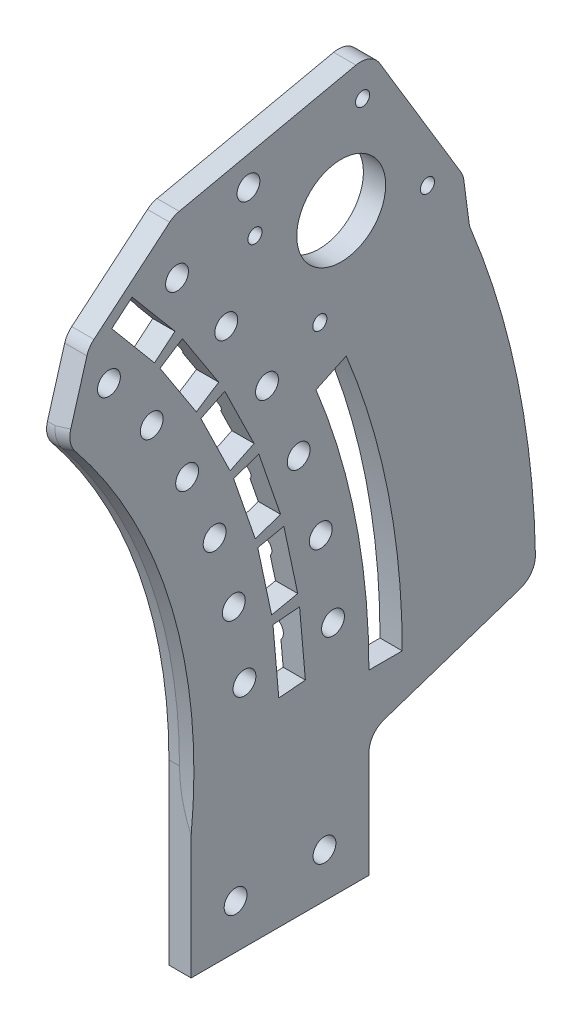
SolidWorks part; units mm, degrees
other "Markup1"
sketch "Sketch5" plane through (7.4724, -50.8, -116.7452) normal (0.7166, -0.0822, 0.6926) x (0.6913, -0.0479, -0.721)
other "Markup2"
sketch "Sketch6" plane through (7.4724, -50.8, -116.7452) normal (0.7166, -0.0822, 0.6926) x (0.6913, -0.0479, -0.721)
material "6061-T6 (SS)"
ref_plane "Front Plane" through (0, 0, 0) normal (0, 0, 1) x (1, 0, 0)
ref_plane "Top Plane" through (0, 0, 0) normal (0, 1, 0) x (1, 0, 0)
ref_plane "Right Plane" through (0, 0, 0) normal (1, 0, 0) x (0, 0, -1)
sketch "Sketch1" plane through (0, 0, 0) normal (1, 0, 0) x (0, 0, -1)
  line L0 (0, 0) -> (152.4, 0) construction
  line L1 (0, 0) -> (116.7452, 97.9608) construction
  line L2 (152.4, 0) -> (152.4, -50.8)
  line L3 (152.4, -50.8) -> (203.2, -50.8)
  line L4 (203.2, -50.8) -> (203.2, 0) construction
  line L5 (116.7452, 97.9608) -> (148.2956, 124.4347) construction
  line L6 (152.4, 0) -> (203.2, 0) construction
  line L7 (116.7452, 97.9608) -> (148.2956, 124.4347) construction
  line L8 (0, 0) -> (177.1234, 15.4963) construction
  line L9 (0, 0) -> (0, 168.3639) construction
  line L10 (177.1234, 15.4963) -> (183.4493, 16.0497) construction
  line L11 (0, 0) -> (175.0988, 30.8746) construction
  line L12 (0, 0) -> (171.7416, 46.018) construction
  line L13 (0, 0) -> (167.0773, 60.8112) construction
  line L14 (0, 0) -> (161.1415, 75.1415) construction
  line L15 (0, 0) -> (153.9793, 88.9) construction
  line L16 (0, 0) -> (145.6452, 101.9819) construction
  line L17 (0, 0) -> (175.0988, 30.8746) construction
  line L18 (0, 0) -> (171.7416, 46.018) construction
  line L19 (183.4493, 16.0497) -> (196.1009, 17.1566) construction
  line L20 (181.3523, 31.9773) -> (193.8594, 34.1826) construction
  line L21 (177.8752, 47.6615) -> (190.1425, 50.9485) construction
  line L22 (173.0444, 62.983) -> (184.9785, 67.3267) construction
  line L23 (166.8966, 77.8252) -> (178.4067, 83.1924) construction
  line L24 (159.4786, 92.075) -> (170.4771, 98.425) construction
  line L25 (150.8468, 105.6241) -> (161.2501, 112.9085) construction
  line L26 (0, 0) -> (183.4493, 16.0497) construction
  line L27 (0, 0) -> (181.3523, 31.9773) construction
  line L28 (152.4, -50.8) -> (152.4, -38.1) construction
  line L29 (152.4, -38.1) -> (203.2, -38.1) construction
  line L30 (0, 0) -> (42824.6192, 25807.9831) construction
  line L31 (195.2803, 117.6844) -> (182.1698, 139.4393) construction
  line L32 (195.2803, 117.6844) -> (208.3907, 95.9295) construction
  line L33 (217.0352, 130.7949) -> (203.9247, 152.5498)
  line L34 (217.0352, 130.7949) -> (230.1456, 109.04)
  line L36 (177.6941, 146.8661) -> (203.9247, 152.5498)
  line L37 (196.7125, 80.97) -> (212.8664, 88.5027) construction
  line L38 (188.0704, 76.9401) -> (212.8664, 88.5027) construction
  line L39 (212.8664, 88.5027) -> (230.1456, 109.04) construction
  line L40 (196.7125, 80.97) -> (188.0704, 76.9401)
  line L41 (203.2, 0) -> (212.725, 0)
  line L42 (203.2, -15.875) -> (250.825, 0)
  line L43 (230.1456, 109.04) -> (231.9445, 95.472)
  line L44 (203.2, -50.8) -> (203.2, -15.875)
  line L45 (195.2803, 117.6844) -> (190.7375, 99.3622) construction
  line L47 (0, 0) -> (136.2027, 114.2876) construction
  line L48 (116.7452, 97.9608) -> (123.1425, 119.9075)
  line L49 (123.1425, 119.9075) -> (147.4644, 140.316)
  line L50 (147.4644, 140.316) -> (177.6941, 146.8661)
  line L51 (189.1677, 93.0309) -> (195.2803, 117.6844) construction
  line L52 (195.2803, 117.6844) -> (201.3928, 142.3379) construction
  arc A0 (152.4, 0) -> (116.7452, 97.9608) centre (0, 0) ccw
  arc A1 (203.2, 0) -> (188.0704, 76.9401) centre (0, 0) ccw
  circle A2 centre (177.1234, 15.4963) radius 6.35 construction
  arc A4 (183.4493, 16.0497) -> (141.0671, 118.3693) centre (0, 0) ccw construction
  arc A5 (189.7751, 16.6032) -> (145.9315, 122.451) centre (0, 0) ccw construction
  circle A7 centre (196.1009, 17.1566) radius 6.35 construction
  circle A9 centre (175.0988, 30.8746) radius 6.35 construction
  circle A11 centre (171.7416, 46.018) radius 6.35 construction
  circle A13 centre (167.0773, 60.8112) radius 6.35 construction
  circle A15 centre (161.1415, 75.1415) radius 6.35 construction
  circle A17 centre (153.9793, 88.9) radius 6.35 construction
  circle A19 centre (145.6452, 101.9819) radius 6.35 construction
  circle A21 centre (193.8594, 34.1826) radius 6.35 construction
  circle A23 centre (190.1425, 50.9485) radius 6.35 construction
  circle A25 centre (184.9785, 67.3267) radius 6.35 construction
  circle A27 centre (178.4067, 83.1924) radius 6.35 construction
  circle A29 centre (170.4771, 98.425) radius 6.35 construction
  circle A31 centre (161.2501, 112.9085) radius 6.35 construction
  circle A32 centre (165.1, -38.1) radius 3.2639
  circle A33 centre (190.5, -38.1) radius 3.2639
  circle A34 centre (195.2803, 117.6844) radius 12.7
  circle A36 centre (208.3907, 95.9295) radius 2.0193 construction
  arc A37 (196.7125, 80.97) -> (212.725, 0) centre (0, 0) cw
  arc A38 (231.9445, 95.472) -> (250.825, 0) centre (0, 0) cw
  circle A41 centre (170.6267, 123.797) radius 2.0193
  circle A42 centre (201.3928, 142.3379) radius 2.0193
  circle A45 centre (195.2803, 117.6844) radius 12.7
  circle A46 centre (219.9338, 111.5719) radius 2.0193
  circle A47 centre (195.2803, 117.6844) radius 12.7
  circle A48 centre (189.1677, 93.0309) radius 2.0193
  circle A49 centre (195.2803, 117.6844) radius 12.7
  point P11 (151.8201, 13.2825)
  point P24 (150.0847, 26.464)
  point P82 (217.0352, 130.7949)
  point P124 (195.2803, 117.6844)
  dimension "D5" = 12.7
  dimension "D7" = 22.86
  dimension "D12" = 12.7
  dimension "D24" = 6.5278
  dimension "D25" = 6.5278
  dimension "D28" = 25.4
  dimension "D30" = 25.4
  dimension "D32" = 4.0386
  dimension "D35" = 9.525
  dimension "D43" = 4.0386
  dimension "D1" = 152.4
  dimension "D2" = 40
  dimension "D3" = 50.8
  dimension "D4" = 50.8
  dimension "D6" = 5
  dimension "D8" = 25.4
  dimension "D10" = 90
  dimension "D13" = 25.4
  dimension "D14" = 5
  dimension "D16" = 5
  dimension "D17" = 6.35
  dimension "D20" = 5
  dimension "D21" = 12.7
  dimension "D22" = 12.7
  dimension "D23" = 12.7
  dimension "D26" = 8.925
  dimension "D27" = 228
  dimension "D29" = 25.4
  dimension "D31" = 25.4
  dimension "D33" = 25.4
  dimension "D34" = 25.4
  dimension "D37" = 15.875
  dimension "D38" = 45
  dimension "D41" = 12.7
  dimension "D42" = 31.75
  dimension "D9" = 6.35
  dimension "D36" = 38.1
  dimension "D15" = 6
  dimension "D19" = 7
  dimension "D45" = 4
extrude "Boss-Extrude1" add sketch "Sketch1" along normal blind 6.35 contours A38 L43 L34 L33 L36 L50 L49 L48 A0 L2 L3 L44 L42 A48 A46 A42 A41 A34 A33 A32 region at (0, 54.4796, -185.6582)
sketch "Sketch2" plane through (0, 0, 0) normal (0, 1, 0) x (1, 0, 0)
  line L0 (0, 0) -> (31.75, 0) construction
  line L1 (31.75, 0) -> (31.75, 38.1) construction
  line L2 (31.75, 38.1) -> (-86.106, 38.1)
  line L3 (-86.106, 38.1) -> (149.606, 38.1)
  arc A0 (149.606, 38.1) -> (-86.106, 38.1) centre (31.75, 38.1) ccw
  dimension "D3" = 235.712
  dimension "D1" = 31.75
  dimension "D2" = 38.1
revolve "Cut-Revolve1" cut sketch "Sketch2" angle 360 about L0 region at (31.75, 0, -88.1196)
fillet "Fillet1" radius 6.35 9 edges at (3.175, -15.875, -203.2) (3.175, 0, -250.825) (3.175, 95.472, -231.9445) (3.175, 109.04, -230.1456) (3.175, 152.5498, -203.9247) (3.175, 140.316, -147.4644) (3.175, 119.9075, -123.1425) (1.5088, 97.9608, -116.7452)
sketch "Sketch7" plane through (0, 0, 0) normal (0, 0, 1) x (1, 0, 0)
  line L0 (0, 0) -> (50000, 0) construction
sketch "Sketch8" plane through (0, 0, 0) normal (-1, 0, 0) x (0, 0, 1)
  line L0 (0, 0) -> (-192.938, 16.8799) construction
  line L1 (0, 0) -> (-81.6847, 0) construction
  line L2 (0, 0) -> (-189.4427, 40.2673) construction
  line L3 (0, 0) -> (-183.1233, 63.0544) construction
  line L4 (0, 0) -> (-174.0739, 84.9015) construction
  line L5 (0, 0) -> (-162.4295, 105.483) construction
  line L6 (0, 0) -> (-148.3637, 124.4919) construction
  line L7 (0, 0) -> (-167.6347, 14.6661) construction
  line L8 (0, 0) -> (-164.5978, 34.9863) construction
  line L9 (-177.4475, 5.9633) -> (-175.7872, 24.9408)
  line L10 (-175.7872, 24.9408) -> (-183.3782, 25.6049)
  line L11 (-183.3782, 25.6049) -> (-185.0385, 6.6274)
  line L12 (-185.0385, 6.6274) -> (-177.4475, 5.9633)
  line L13 (-182.8516, 29.1285) -> (-175.3981, 27.5442)
  line L14 (-175.3981, 27.5442) -> (-171.4374, 46.1779)
  line L15 (-171.4374, 46.1779) -> (-178.8909, 47.7622)
  line L16 (-178.8909, 47.7622) -> (-182.8516, 29.1285)
  line L17 (-177.9388, 51.1954) -> (-170.7339, 48.7146)
  line L18 (-170.7339, 48.7146) -> (-164.5318, 66.7267)
  line L19 (-164.5318, 66.7267) -> (-171.7367, 69.2075)
  line L20 (-171.7367, 69.2075) -> (-177.9388, 51.1954)
  line L21 (-170.3733, 72.4991) -> (-163.5245, 69.1587)
  line L22 (-163.5245, 69.1587) -> (-155.1735, 86.2807)
  line L23 (-155.1735, 86.2807) -> (-162.0223, 89.6211)
  line L24 (-162.0223, 89.6211) -> (-170.3733, 72.4991)
  line L25 (-160.2679, 92.722) -> (-153.8773, 88.5718)
  line L26 (-153.8773, 88.5718) -> (-143.5019, 104.5485)
  line L27 (-143.5019, 104.5485) -> (-149.8926, 108.6986)
  line L28 (-149.8926, 108.6986) -> (-160.2679, 92.722)
  line L29 (-147.7734, 111.5626) -> (-141.9361, 106.6645)
  line L30 (-141.9361, 106.6645) -> (-129.691, 121.2577)
  line L31 (-129.691, 121.2577) -> (-135.5283, 126.1557)
  line L32 (-135.5283, 126.1557) -> (-147.7734, 111.5626)
  circle A0 centre (-192.938, 16.8799) radius 3.2639
  circle A2 centre (-167.6347, 14.6661) radius 3.2639
  circle A3 centre (-189.4427, 40.2673) radius 3.2639
  circle A4 centre (-164.5978, 34.9863) radius 3.2639
  circle A5 centre (-183.1233, 63.0544) radius 3.2639
  circle A6 centre (-159.1071, 54.785) radius 3.2639
  circle A7 centre (-174.0739, 84.9015) radius 3.2639
  circle A8 centre (-151.2446, 73.7669) radius 3.2639
  circle A9 centre (-162.4295, 105.483) radius 3.2639
  circle A10 centre (-141.1273, 91.6491) radius 3.2639
  circle A11 centre (-148.3637, 124.4919) radius 3.2639
  circle A12 centre (-128.9061, 108.1651) radius 3.2639
  dimension "D3" = 6.5278
  dimension "D4" = 6.5278
  dimension "D1" = 193.675
  dimension "D2" = 5
  dimension "D5" = 25.4
  dimension "D7" = 7
  dimension "D8" = 19.05
  dimension "D9" = 7.62
  dimension "D10" = 9.525
  dimension "D11" = 9.017
  dimension "D6" = 6
extrude "Cut-Extrude1" cut sketch "Sketch8" against normal through all
sketch "Sketch9" plane through (0, 16.1161, -184.2084) normal (0, -0.0872, 0.9962) x (1, 0, 0)
  line L0 (0, 0) -> (-2.3812, 0) construction
  line L1 (0, 9.525) -> (0, -9.525) construction
  circle A0 centre (-2.3812, 0) radius 3.2639
  dimension "D1" = 6.5278
  dimension "D2" = 2.3812
extrude "Cut-Extrude2" cut sketch "Sketch9" against normal blind 3.175 and the other way blind 10.033
pattern_circular "CirPattern1" count 6 every 7 about axis through (0, 0, 0) along (1, 0, 0) of "Cut-Extrude2"
sketch "Sketch10" plane through (0, 0, 0) normal (-1, 0, 0) x (0, 0, 1)
  line L0 (0, 0) -> (-168.7728, 136.6695) construction
  line L1 (0, 0) -> (-65.3997, 0) construction
  circle A0 centre (-168.7728, 136.6695) radius 3.2639
  dimension "D1" = 6.5278
  dimension "D2" = 217.17
  dimension "D3" = 39
extrude "Cut-Extrude3" cut sketch "Sketch10" against normal through all
